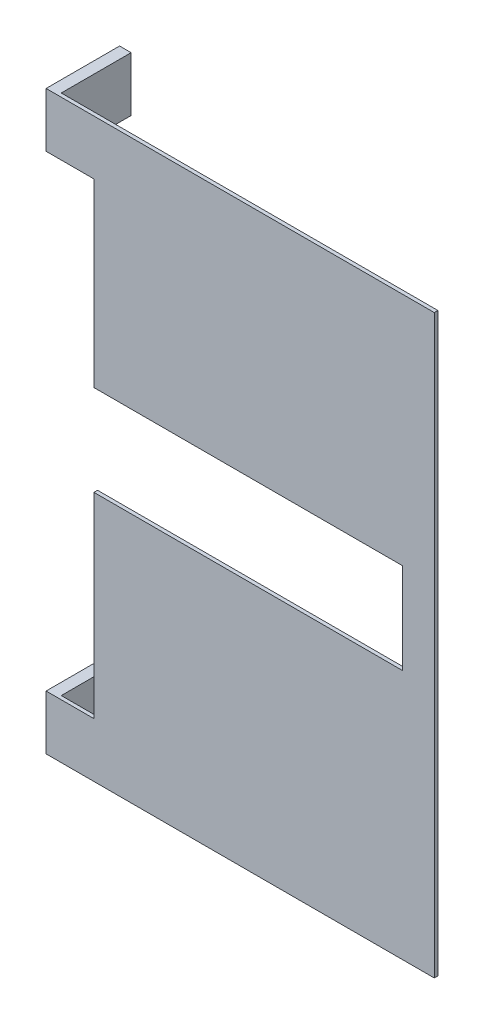
SolidWorks part; units mm, degrees
ref_plane "Front Plane" through (0, 0, 0) normal (0, 0, 1) x (1, 0, 0)
ref_plane "Top Plane" through (0, 0, 0) normal (0, 1, 0) x (1, 0, 0)
ref_plane "Right Plane" through (0, 0, 0) normal (1, 0, 0) x (0, 0, -1)
sketch "Sketch1" plane through (0, 0, 0) normal (0, 0, 1) x (1, 0, 0)
  line L0 (2.5917, 2.54) -> (2.5917, -124.46)
  line L7 (-72.4142, -124.46) -> (2.5917, -124.46)
  line L8 (2.5917, 2.54) -> (-72.4142, 2.54)
  line L9 (2.5917, 2.54) -> (-80.4142, 2.54) construction
  line L10 (-72.4142, 2.54) -> (-72.4142, -121.92)
  line L11 (2.5917, -121.92) -> (-80.4142, -121.92) construction
  line L12 (-72.4142, -121.92) -> (-72.4142, -124.46)
  dimension "D1" = 8
extrude "Boss-Extrude1" add sketch "Sketch1" along normal blind 0.8
sketch "Sketch2" plane through (0, 0, 0) normal (0, 0, 1) x (1, 0, 0)
  line L0 (-72.4142, 2.54) -> (-80.4142, 2.54)
  line L2 (-80.4142, -35.96) -> (-80.4142, 2.54) construction
  line L3 (-80.4142, -9.46) -> (-72.4142, -9.46)
  line L4 (-72.4142, 2.54) -> (-72.4142, -124.46) construction
  line L5 (-74.3384, -10.46) -> (-83.9948, -10.46) construction
  line L6 (-72.4142, -124.46) -> (-80.4142, -124.46)
  line L8 (-80.4142, -124.46) -> (-80.4142, -85.96) construction
  line L9 (-80.4142, -112.46) -> (-72.4142, -112.46)
  line L10 (-72.4142, -112.46) -> (-72.4142, -124.46)
  line L11 (-83.9948, -111.46) -> (-74.3384, -111.46) construction
  line L12 (-72.4142, 2.54) -> (-72.4142, -9.46)
  line L13 (-80.4142, 2.54) -> (-82.9542, 2.54)
  line L14 (-82.9542, 2.54) -> (-82.9542, -9.46)
  line L15 (-82.9542, -35.96) -> (-82.9542, 2.54) construction
  line L16 (-82.9542, -9.46) -> (-80.4142, -9.46)
  line L17 (-80.4142, -124.46) -> (-82.9542, -124.46)
  line L18 (-82.9542, -124.46) -> (-82.9542, -112.46)
  line L19 (-82.9542, -124.46) -> (-82.9542, -85.96) construction
  line L20 (-82.9542, -112.46) -> (-80.4142, -112.46)
  dimension "D1" = 1
  dimension "D2" = 1
extrude "Boss-Extrude2" add sketch "Sketch2" along normal blind 0.8
sketch "Sketch3" plane through (0, 0, 0) normal (0, 0, -1) x (-1, 0, 0)
  line L0 (82.9542, 2.54) -> (80.4142, 2.54)
  line L1 (80.4142, 2.54) -> (80.4142, 0) construction
  line L2 (-2.5917, 2.54) -> (82.9542, 2.54) construction
  line L3 (80.4142, 2.54) -> (80.4142, -9.46)
  line L4 (82.9542, -9.46) -> (72.4142, -9.46) construction
  line L5 (80.4142, -9.46) -> (82.9542, -9.46)
  line L6 (82.9542, -9.46) -> (82.9542, 2.54)
  line L7 (82.9542, -124.46) -> (80.4142, -124.46)
  line L8 (82.9542, -124.46) -> (-2.5917, -124.46) construction
  line L9 (80.4142, -121.92) -> (80.4142, -124.46) construction
  line L10 (80.4142, -124.46) -> (80.4142, -112.46)
  line L11 (72.4142, -112.46) -> (82.9542, -112.46) construction
  line L12 (80.4142, -112.46) -> (82.9542, -112.46)
  line L13 (82.9542, -112.46) -> (82.9542, -124.46)
extrude "Boss-Extrude3" add sketch "Sketch3" along normal up to surface (15.4 mm away) up to face at (2.5917, -60.96, 0.4)
sketch "Sketch4" plane through (0, 0, 0.8) normal (0, 0, 1) x (1, 0, 0)
  line L0 (-4.4142, -49.2778) -> (-72.4142, -49.2778)
  line L1 (-72.4142, -9.46) -> (-72.4142, -112.46) construction
  line L2 (-72.4142, -49.2778) -> (-72.4142, -69.2778)
  line L3 (-72.4142, -69.2778) -> (-4.4142, -69.2778)
  line L4 (-4.4142, -69.2778) -> (-4.4142, -49.2778)
  dimension "D1" = 68
  dimension "D2" = 20
extrude "Cut-Extrude1" cut sketch "Sketch4" against normal through all
